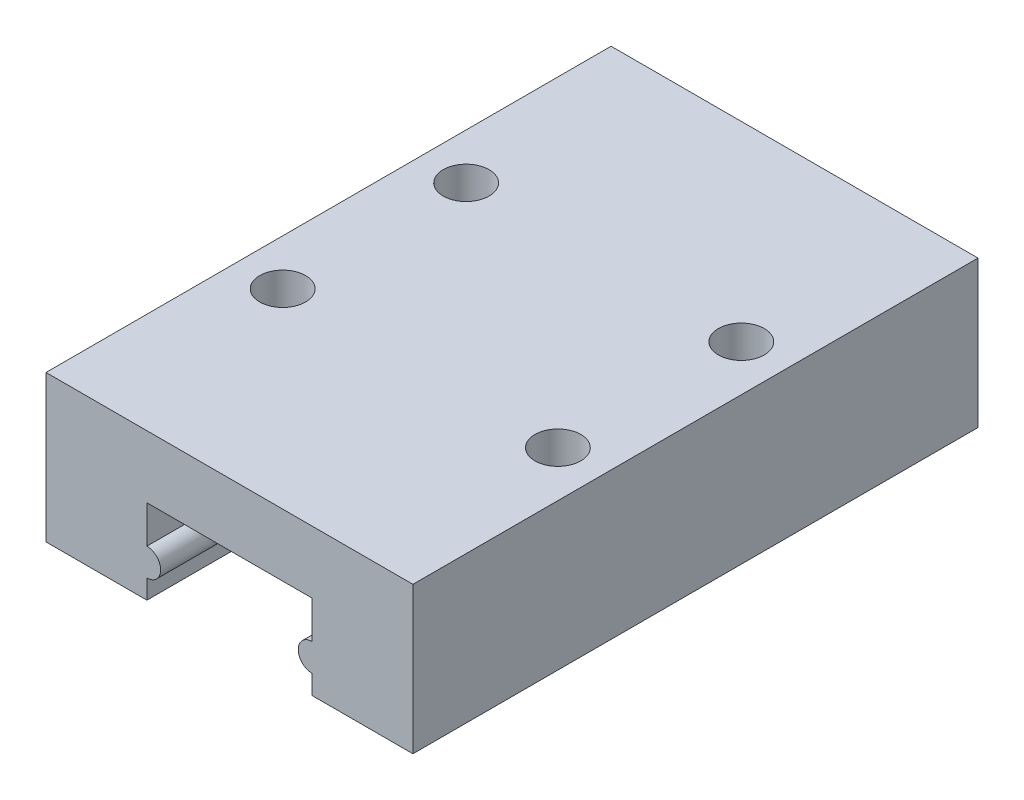
SolidWorks part; units mm, degrees
ref_plane "前视基准面" through (0, 0, 0) normal (0, 0, 1) x (1, 0, 0)
ref_plane "上视基准面" through (0, 0, 0) normal (0, 1, 0) x (1, 0, 0)
ref_plane "右视基准面" through (0, 0, 0) normal (1, 0, 0) x (0, 0, -1)
sketch "草图1" plane through (0, 0, 0) normal (0, 0, 1) x (1, 0, 0)
  line L0 (0, 0) -> (0, 26.2091) construction
  line L1 (-4.5, 0) -> (-4.5, 1.05)
  line L2 (-10, 8) -> (10, 8)
  line L3 (-10, 8) -> (-10, 0)
  line L4 (-10, 0) -> (-4.5, 0)
  line L5 (10, 8) -> (10, 0)
  line L6 (-4.5, 4.6) -> (4.5, 4.6)
  line L7 (4.5, 4.6) -> (4.5, 2.55)
  line L8 (-4.5, 1.8) -> (4.5, 1.8) construction
  line L9 (-4.5, 2.55) -> (-4.5, 4.6)
  line L10 (4.5, 1.05) -> (4.5, 0)
  line L11 (4.5, 0) -> (10, 0)
  line L12 (-4.5, 0) -> (-4.5, -2.2) construction
  line L13 (-4.5, -2.2) -> (4.5, -2.2) construction
  line L14 (4.5, -2.2) -> (4.5, 0) construction
  line L15 (-4.5, 4.3) -> (4.5, 4.3) construction
  arc A0 (-4.5, 1.05) -> (-4.5, 2.55) centre (-4.5, 1.8) ccw
  arc A1 (4.5, 2.55) -> (4.5, 1.05) centre (4.5, 1.8) ccw
  dimension "D5" = 0.75
  dimension "D6" = 0.75
  dimension "D1" = 20
  dimension "D2" = 8
  dimension "D3" = 9
  dimension "D4" = 2.2
  dimension "D7" = 4
  dimension "D8" = 6.5
  dimension "D9" = 0.3
extrude "凸台-拉伸1" add sketch "草图1" along normal blind 30.8
sketch "草图2" plane through (0, 8, 0) normal (0, 1, 0) x (1, 0, 0)
  line L0 (0, 0) -> (0, -30.8) construction
  line L1 (10, -30.8) -> (-10, -30.8) construction
  line L2 (-10, -15.4) -> (10, -15.4) construction
  line L3 (-10, -30.8) -> (-10, 0) construction
  line L4 (10, -30.8) -> (10, 0) construction
  line L5 (10, 0) -> (-10, 0) construction
  circle A0 centre (-7.5, -10.4) radius 1.25
  circle A1 centre (7.5, -10.4) radius 1.25
  circle A2 centre (7.5, -20.4) radius 1.25
  circle A3 centre (-7.5, -20.4) radius 1.25
  dimension "D3" = 2.5
  dimension "D1" = 5
  dimension "D2" = 7.5
  dimension "D4" = 15.4
extrude "切除-拉伸1" cut sketch "草图2" against normal blind 4
cosmetic thread "孔螺蚊线1" parameters "D1"=3, "D2"=3
cosmetic thread "孔螺蚊线2" parameters "D1"=3, "D2"=3
cosmetic thread "孔螺蚊线3" parameters "D1"=3, "D2"=3
cosmetic thread "孔螺蚊线4" parameters "D1"=3, "D2"=3
hole_wizard "M3 螺纹孔1" positions "3D草图1" profile "草图3" tap size "M3" standard "Gb"
sketch3d "3D草图1"
  line L0 (-7.5, 4, 10.4) -> (-7.5, 8, 10.4) construction
  line L1 (-7.5, 4, 20.4) -> (-7.5, 8, 20.4) construction
  line L2 (7.5, 4, 10.4) -> (7.5, 8, 10.4) construction
  line L3 (7.5, 4, 20.4) -> (7.5, 8, 20.4) construction
  point P0 (-7.5, 8, 10.4)
  point P4 (-7.5, 8, 20.4)
  point P8 (7.5, 8, 10.4)
  point P12 (7.5, 8, 20.4)
sketch "草图3" plane through (-7.5, 8, 10.4) normal (1, 0, 0) x (0, 0, 1)
  line L0 (0, 0) -> (0, 3.7511)
  line L1 (0, 3.7511) -> (1.25, 3)
  line L2 (1.25, 3) -> (1.25, 0)
  line L5 (1.25, 0) -> (0, 0)
  line L10 (0, 3.7511) -> (-1.25, 3) construction
  line L11 (0, -6.35) -> (0, 107.95) construction
  dimension "螺纹孔钻头直径" = 2.5
  dimension "螺纹孔钻头深度" = 3
  dimension "导头角度" = 118
